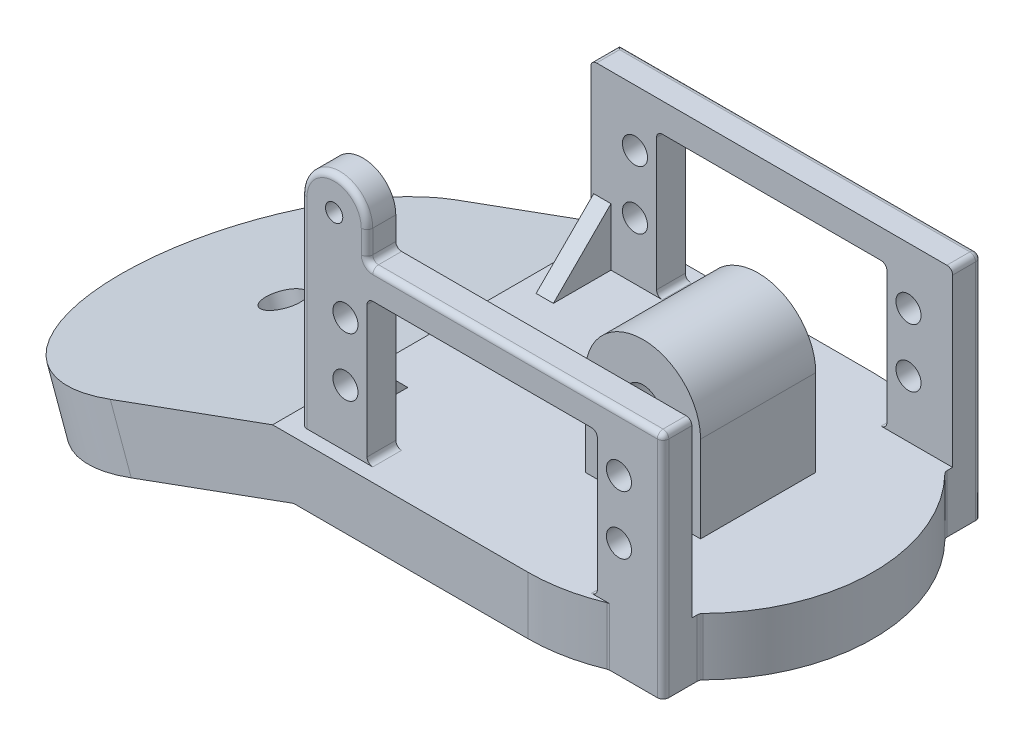
SolidWorks part; units mm, degrees
ref_plane "Plan de face" through (0, 0, 0) normal (0, 0, 1) x (1, 0, 0)
ref_plane "Plan de dessus" through (0, 0, 0) normal (0, 1, 0) x (1, 0, 0)
ref_plane "Plan de droite" through (0, 0, 0) normal (1, 0, 0) x (0, 0, -1)
sketch "Esquisse5" plane through (0, 0, 0) normal (0, 1, 0) x (1, 0, 0)
  line L0 (42.5, 0) -> (-42.5, 0) construction
  line L1 (42.5, -30) -> (-42.5, -30)
  line L2 (42.5, 30) -> (-42.5, 30)
  arc A0 (42.5, -30) -> (42.5, 30) centre (42.5, 0) ccw
  arc A1 (-42.5, 30) -> (-42.5, -30) centre (-42.5, 0) ccw
  point P2 (0, 0)
  dimension "D2" = 30
  dimension "D1" = 85
extrude "Boss.-Extru.3" add sketch "Esquisse5" along normal mid plane 10
sketch "Esquisse36" plane through (0, 0, 0) normal (0, 0, 1) x (1, 0, 0)
  line L0 (0, 0) -> (9.0993, -25)
  line L1 (9.0993, -25) -> (-112.5, -25)
  line L2 (-112.5, -25) -> (-112.5, 35)
  line L3 (-112.5, 35) -> (-12.739, 35)
  line L4 (-12.739, 35) -> (0, 0)
  line L5 (42.5, -5) -> (-42.5, -5) construction
  line L6 (42.5, 5) -> (-42.5, 5) construction
  line L7 (-42.5, 5) -> (-42.5, -5) construction
  dimension "D1" = 180
  dimension "D2" = 20
  dimension "D3" = 70
  dimension "D4" = 30
  dimension "D5" = 70
sketch "Esquisse7" plane through (0, 0, 0) normal (0, 0, 1) x (1, 0, 0)
  line L0 (42.5, 5) -> (32.5, 5)
  line L1 (-42.5, 5) -> (42.5, 5) construction
  line L2 (32.5, 5) -> (32.5, 20)
  line L3 (32.5, 20) -> (52.5, 20)
  line L4 (52.5, 20) -> (52.5, 5)
  line L5 (72.5, 5) -> (42.5, 5) construction
  line L6 (52.5, 5) -> (42.5, 5)
  arc A0 (32.5, 20) -> (52.5, 20) centre (42.5, 20) cw
  circle A1 centre (42.5, 20) radius 3.175
  dimension "D1" = 10
  dimension "D3" = 6.35
  dimension "D2" = 15
extrude "Boss.-Extru.5" add sketch "Esquisse7" along normal mid plane 20 contours A1 L3 A0 | A1 L3 L2 L0 L6 L4 region at (42.5, 12.1572, 0) region at (42.5, 24.5689, 0)
sketch "Esquisse10" plane through (0, -5, 0) normal (0, -1, 0) x (1, 0, 0)
  point P0 (42.5, 0)
ref_plane "Plan1" through (0, 0, 22.64) normal (0, 0, 1) x (1, 0, 0)
sketch "Esquisse13" plane through (0, 0, 22.64) normal (0, 0, 1) x (1, 0, 0)
  line L0 (-42.5, 5) -> (42.5, 5) construction
  line L1 (5.8, 5) -> (58.63, 5)
  line L2 (5.8, 5) -> (5.8, 29.91) construction
  line L3 (5.8, 29.91) -> (58.63, 29.91) construction
  line L4 (58.63, 5) -> (58.63, 29.91) construction
  line L5 (5.8, 5) -> (0.8, 5)
  line L6 (0.8, 5) -> (0.8, 34.91)
  line L7 (0.8, 34.91) -> (63.63, 34.91)
  line L8 (63.63, 34.91) -> (63.63, 5)
  line L9 (63.63, 5) -> (58.63, 5)
  line L10 (63.63, 5) -> (58.63, 5)
  line L11 (0.8, 5) -> (5.8, 5)
  line L12 (12.215, 5) -> (12.215, 29.91)
  line L13 (12.215, 29.91) -> (52.215, 29.91)
  line L14 (52.215, 29.91) -> (52.215, 5)
  line L15 (52.215, 5) -> (12.215, 5)
  circle A0 centre (42.5, 20) radius 3.175 construction
  circle A2 centre (55.97, 25.08) radius 2.18
  circle A3 centre (55.97, 14.92) radius 2.18
  circle A4 centre (8.47, 25.08) radius 2.18
  circle A5 centre (8.47, 14.92) radius 2.18
  point P6 (58.63, 17.455)
  point P24 (32.215, 29.91)
  point P26 (32.215, 34.91)
  dimension "D4" = 5
  dimension "D7" = 4.36
  dimension "D8" = 47.5
  dimension "D12" = 10.16
  dimension "D1" = 52.83
  dimension "D2" = 16.13
  dimension "D3" = 24.91
  dimension "D5" = 4.83
  dimension "D6" = 2.67
  dimension "D9" = 47.5
  dimension "D10" = 0
  dimension "D11" = 0
  dimension "D13" = 0
  dimension "D14" = 5
  dimension "D15" = 5
  dimension "D16" = 40
  dimension "D17" = 0
  dimension "D18" = 0
extrude "Boss.-Extru.8" add sketch "Esquisse13" along normal blind 5 contours L13 L14 L1 L9 L8 L7 L6 L5 L12 A5 A4 A3 A2 region at (3.3, 5.6959, 22.64)
ref_plane "Plan12" through (2.8, 0, 0) normal (-1, 0, 0) x (0, 0, 1)
mirror "Symétrie2" about plane through (0, 0, 0) normal (0, 0, 1) of "Boss.-Extru.8"
sketch "Esquisse14" plane through (0, 0, 0) normal (0, 0, 1) x (1, 0, 0)
  point P0 (42.5, 20)
sketch "Esquisse33" plane through (0, 5, 0) normal (0, -1, 0) x (1, 0, 0)
  line L0 (54.1632, -27.64) -> (63.63, -27.64) construction
  line L1 (63.63, 27.64) -> (54.1632, 27.64)
  line L2 (63.63, 27.64) -> (63.63, -27.64)
  line L3 (63.63, -27.64) -> (54.1632, -27.64)
  line L4 (54.1632, 27.64) -> (54.1632, -27.64)
  dimension "D1" = 0
  dimension "D2" = 0
extrude "Boss.-Extru.10" add sketch "Esquisse33" along normal up to surface (10 mm away) up to face at (0, -5, 0)
sketch "Esquisse34" plane through (0, 0, 0) normal (0, 1, 0) x (1, 0, 0)
  line L0 (0, 0) -> (0, 29.4868) construction
extrude "Enlèv. mat.-Extru.6" cut sketch "Esquisse36" against normal mid plane 130
ref_plane "Plan11" through (0, 0, 0) normal (-0.342, 0.9397, 0) x (0, 0, -1)
sketch "Esquisse35" plane through (0, 0, 0) normal (-0.342, 0.9397, 0) x (0, 0, -1)
  circle A0 centre (0, 30) radius 30
  dimension "D1" = 60
  dimension "D2" = 0
extrude "Boss.-Extru.11" add sketch "Esquisse35" along normal mid plane 10.64
sketch "Esquisse37" plane through (0, 0, 0) normal (0, 0, 1) x (1, 0, 0)
sketch "Esquisse38" plane through (-1.8195, 4.9992, 0) normal (-0.342, 0.9397, 0) x (0.9397, 0.342, 0)
  point P1 (-30, 0)
sketch "Esquisse39" plane through (1.8195, -4.9992, 0) normal (0.342, -0.9397, 0) x (0.9397, 0.342, 0)
  point P0 (-30, 0)
sketch "Esquisse40" plane through (0, 0, 0) normal (0, 0, 1) x (1, 0, 0)
  line L0 (-26.3712, -15.2598) -> (-30.0103, -5.2614)
  line L1 (-26.3712, -15.2598) -> (1.8195, -4.9992)
  line L2 (-30.0103, -5.2614) -> (-1.8195, 4.9992)
  line L3 (1.8195, -4.9992) -> (-1.8195, 4.9992)
  dimension "D1" = 0
extrude "Boss.-Extru.12" add sketch "Esquisse40" along normal mid plane 60
sketch "Esquisse41" plane through (-1.8195, 4.9992, 0) normal (-0.342, 0.9397, 0) x (0.9397, 0.342, 0)
  circle A0 centre (-30, 0) radius 3.175
  dimension "D1" = 6.35
extrude "Enlèv. mat.-Extru.7" cut sketch "Esquisse41" against normal blind 60
sketch "Esquisse42" plane through (0, 0, 27.64) normal (0, 0, 1) x (1, 0, 0)
  line L0 (0.8, 34.91) -> (0.8, 39.91)
  line L1 (0.8, 39.91) -> (12.215, 39.91)
  line L2 (12.215, 39.91) -> (12.215, 34.91)
  line L3 (0.8, 34.91) -> (63.63, 34.91) construction
  line L4 (12.215, 34.91) -> (0.8, 34.91)
  line L5 (12.215, 5) -> (12.215, 29.91) construction
  arc A0 (0.8, 39.91) -> (12.215, 39.91) centre (6.5075, 39.91) cw
  circle A1 centre (6.5075, 39.91) radius 1.5
  line M15 (63.63, 34.91) -> (0.8, 34.91)
  dimension "D3" = 3
  dimension "D1" = 5
  dimension "D2" = 0
extrude "Boss.-Extru.13" add sketch "Esquisse42" against normal up to surface (5 mm away) contours A1 L1 A0 | A1 L1 L0 L2 M15 region at (6.5075, 37.287, 27.64) region at (6.5075, 42.4648, 27.64) up to face at (10.65, 14.92, 22.64)
sketch "Esquisse45" plane through (2.8, 0, 0) normal (-1, 0, 0) x (0, 0, 1)
  line L0 (22.64, 14.9996) -> (12.64, 4.9996)
  line L1 (22.64, 5) -> (22.64, 39.91) construction
  line L2 (30, 4.9996) -> (-30, 4.9996) construction
  dimension "D1" = 10
  dimension "D2" = 10
rib "Nervure4" sketch "Esquisse45" sketch "Esquisse45" thickness 3 extrusion direction parallel to sketch draft on no parameters "D1"=3
fillet "Congé1" radius 1 6 edges at (54.1632, 0, 27.64) (63.63, 14.955, 27.64) (63.63, 0, 21.2961) (54.1632, 0, -27.64) (63.63, 0, -21.2961) (63.63, 14.955, -27.64)
mirror "Symétrie3" about plane through (0, 0, 0) normal (0, 0, 1) of "Nervure4"
fillet "Congé2" radius 1 19 edges at (0.8, 22.455, 27.64) (6.5075, 45.6175, 27.64) (12.215, 37.41, 27.64) (31.715, 34.91, -27.64) (63.3371, 34.91, -27.3471) (37.4225, 34.91, 27.64) (63.3371, 34.91, 27.3471) (63.63, 34.91, -24.64) (0.8, 34.91, -25.14) (52.215, 5, -25.14) (52.215, 29.91, -25.14) (12.215, 29.91, -25.14) (12.215, 5, -25.14) (12.215, 5, 25.14) (52.215, 5, 25.14) (52.215, 29.91, 25.14) (12.215, 29.91, 25.14) (12.215, 34.91, 25.14) (63.63, 34.91, 24.64)
